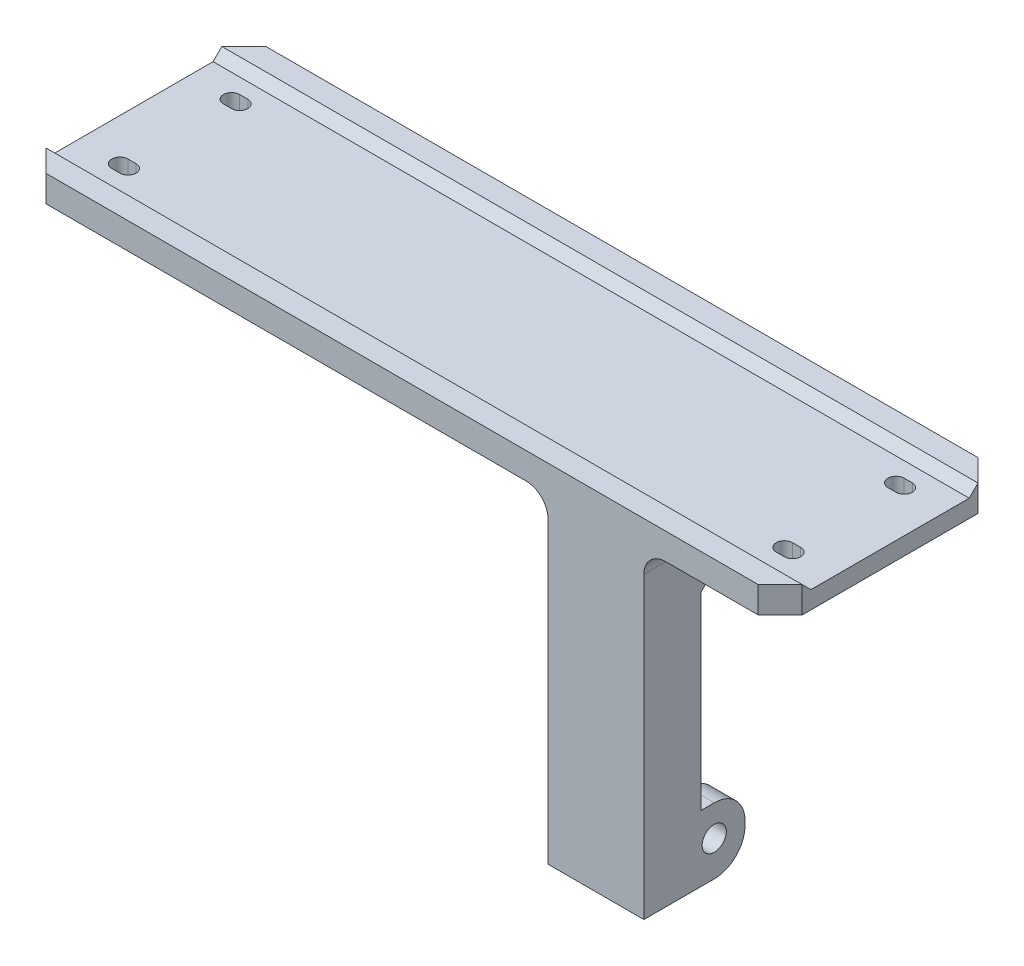
SolidWorks part; units mm, degrees
ref_plane "Front Plane" through (0, 0, 0) normal (0, 0, 1) x (1, 0, 0)
ref_plane "Top Plane" through (0, 0, 0) normal (0, 1, 0) x (1, 0, 0)
ref_plane "Right Plane" through (0, 0, 0) normal (1, 0, 0) x (0, 0, -1)
sketch "Sketch1" plane through (0, 0, 0) normal (0, 0, 1) x (1, 0, 0)
  line L1 (-86, 2) -> (86, 2)
  line L2 (-86, 2) -> (-86, -2)
  line L3 (-86, -2) -> (86, -2)
  line L4 (86, 2) -> (86, -2)
  line L5 (-86, 2) -> (86, -2) construction
  line L6 (-86, -2) -> (86, 2) construction
  point P0 (0, 0)
  dimension "D1" = 172
  dimension "D2" = 4
extrude "Boss-Extrude1" add sketch "Sketch1" along normal blind 50
sketch "Sketch2" plane through (0, 2, 0) normal (0, 1, 0) x (1, 0, 0)
  line L1 (86, -50) -> (86, 0) construction
  line L2 (86, 0) -> (-86, 0) construction
  line L3 (-76.5, -10.45) -> (-74.65, -10.45)
  line L4 (-74.65, -14.15) -> (-76.5, -14.15)
  line L5 (74.65, -10.45) -> (76.5, -10.45)
  line L6 (74.65, -14.15) -> (76.5, -14.15)
  line L7 (-76.5, -35.85) -> (-74.65, -35.85)
  line L8 (-74.65, -39.55) -> (-76.5, -39.55)
  line L9 (74.65, -35.85) -> (76.5, -35.85)
  line L10 (74.65, -39.55) -> (76.5, -39.55)
  arc A0 (-76.5, -10.45) -> (-76.5, -14.15) centre (-76.5, -12.3) ccw
  arc A1 (-74.65, -14.15) -> (-74.65, -10.45) centre (-74.65, -12.3) ccw
  arc A2 (74.65, -10.45) -> (74.65, -14.15) centre (74.65, -12.3) ccw
  arc A3 (76.5, -14.15) -> (76.5, -10.45) centre (76.5, -12.3) ccw
  arc A4 (-76.5, -35.85) -> (-76.5, -39.55) centre (-76.5, -37.7) ccw
  arc A5 (-74.65, -39.55) -> (-74.65, -35.85) centre (-74.65, -37.7) ccw
  arc A6 (76.5, -39.55) -> (76.5, -35.85) centre (76.5, -37.7) ccw
  arc A7 (74.65, -35.85) -> (74.65, -39.55) centre (74.65, -37.7) ccw
  dimension "D1" = 3.7
  dimension "D2" = 3.7
  dimension "D3" = 153
  dimension "D4" = 9.5
  dimension "D5" = 12.3
  dimension "D6" = 12.3
  dimension "D7" = 2
extrude "Cut-Extrude1" cut sketch "Sketch2" against normal blind 50
sketch "Sketch3" plane through (0, 0, 50) normal (0, 0, 1) x (1, 0, 0)
  line L0 (-86, -2) -> (86, -2) construction
  line L1 (60.6, -2) -> (25.6, -2)
  line L2 (60.6, -2) -> (60.6, -75)
  line L3 (60.6, -75) -> (25.6, -75)
  line L4 (25.6, -2) -> (25.6, -75)
  line L5 (86, -2) -> (86, 2) construction
  dimension "D1" = 25.4
  dimension "D2" = 35
  dimension "D3" = 73
extrude "Boss-Extrude2" add sketch "Sketch3" against normal blind 3
sketch "Sketch4" plane through (0, 0, 47) normal (0, 0, -1) x (-1, 0, 0)
  line L0 (-25.6, -75) -> (-60.6, -75) construction
  line L1 (-45.5, -75) -> (-42.7, -75)
  line L2 (-45.5, -75) -> (-45.5, -60)
  line L3 (-45.5, -60) -> (-42.7, -60)
  line L4 (-42.7, -75) -> (-42.7, -60)
  line L6 (-39.2, -60) -> (-33.2, -60)
  line L7 (-39.2, -60) -> (-39.2, -75)
  line L8 (-39.2, -75) -> (-33.2, -75)
  line L9 (-33.2, -60) -> (-33.2, -75)
  line L10 (-49, -60) -> (-55, -60)
  line L11 (-49, -60) -> (-49, -75)
  line L12 (-49, -75) -> (-55, -75)
  line L13 (-55, -60) -> (-55, -75)
  line L14 (-86, -2) -> (-86, 2) construction
  dimension "D1" = 15
  dimension "D2" = 15
  dimension "D3" = 15
  dimension "D4" = 2.8
  dimension "D5" = 3.5
  dimension "D6" = 3.5
  dimension "D7" = 6
  dimension "D8" = 6
  dimension "D9" = 37
extrude "Boss-Extrude3" add sketch "Sketch4" along normal blind 20
fillet "Fillet1" radius 7 6 edges at (36.2, -75, 27) (44.1, -75, 27) (52, -75, 27) (36.2, -60, 27) (44.1, -60, 27) (52, -60, 27)
sketch "Sketch5" plane through (55, 0, 0) normal (1, 0, 0) x (0, 0, -1)
  line L0 (-27, -67) -> (-27, -68) construction
  circle A0 centre (-34, -67) radius 2.75
  dimension "D1" = 5.5
  dimension "D2" = 7
extrude "Cut-Extrude2" cut sketch "Sketch5" against normal blind 30
sketch "Sketch6" plane through (0, 0, 47) normal (0, 0, -1) x (-1, 0, 0)
  line L1 (-55, -75) -> (-60.6, -75)
  line L2 (-55, -75) -> (-55, -2)
  line L3 (-55, -2) -> (-60.6, -2)
  line L4 (-60.6, -75) -> (-60.6, -2)
  line L5 (-33.2, -75) -> (-25.6, -75)
  line L6 (-33.2, -75) -> (-33.2, -2)
  line L7 (-33.2, -2) -> (-25.6, -2)
  line L8 (-25.6, -75) -> (-25.6, -2)
extrude "Cut-Extrude3" cut sketch "Sketch6" against normal blind 20
sketch "Sketch7" plane through (0, 0, 47) normal (0, 0, -1) x (-1, 0, 0)
  line L0 (-55, -2) -> (-33.2, -2) construction
  line L1 (-55, -60) -> (-49, -60)
  line L2 (-55, -60) -> (-55, -2)
  line L3 (-55, -2) -> (-49, -2)
  line L4 (-49, -60) -> (-49, -2)
  line L6 (-33.2, -60) -> (-39.2, -60)
  line L7 (-33.2, -60) -> (-33.2, -2)
  line L8 (-33.2, -2) -> (-39.2, -2)
  line L9 (-39.2, -60) -> (-39.2, -2)
  dimension "D1" = 6
  dimension "D2" = 6
extrude "Boss-Extrude4" add sketch "Sketch7" along normal blind 10
chamfer "Chamfer1" distance 10 angle 45 1 edges at (44.1, -60, 47)
chamfer "Chamfer2" distance 15 angle 45 2 edges at (36.2, -2, 37) (52, -2, 37)
fillet "Fillet2" radius 5 2 edges at (33.2, -2, 36) (55, -2, 36)
sketch "Sketch8" plane through (0, 2, 0) normal (0, 1, 0) x (1, 0, 0)
  line L0 (86, -50) -> (86, 0) construction
  line L1 (-86, 0) -> (86, 0)
  line L2 (-86, 0) -> (-86, -4)
  line L3 (-86, -4) -> (86, -4)
  line L4 (86, 0) -> (86, -4)
  line L5 (-86, -50) -> (-86, 0) construction
  line L6 (86, -50) -> (-86, -50)
  line L7 (86, -50) -> (86, -46)
  line L8 (86, -46) -> (-86, -46)
  line L9 (-86, -50) -> (-86, -46)
  dimension "D1" = 4
  dimension "D2" = 4
extrude "Boss-Extrude5" add sketch "Sketch8" along normal blind 2
chamfer "Chamfer3" distance 3 angle 45 2 edges at (0, 2, 46) (0, 2, 4)
chamfer "Chamfer4" distance 5 angle 45 4 edges at (-86, 1, 0) (-86, 1, 50) (86, 1, 50) (86, 1, 0)
